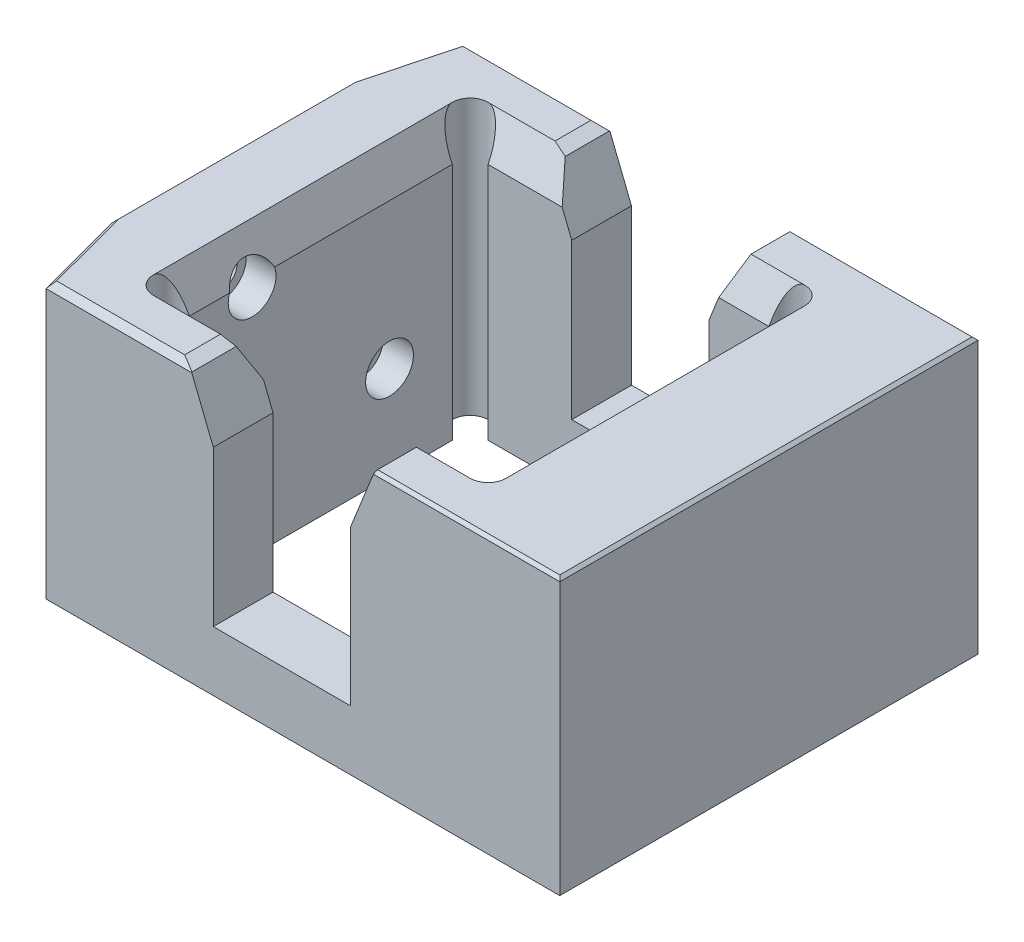
SolidWorks part; units mm, degrees
ref_plane "Front Plane" through (0, 0, 0) normal (0, 0, 1) x (1, 0, 0)
ref_plane "Top Plane" through (0, 0, 0) normal (0, 1, 0) x (1, 0, 0)
ref_plane "Right Plane" through (0, 0, 0) normal (1, 0, 0) x (0, 0, -1)
sketch "Sketch1" plane through (0, 0, 0) normal (0, 1, 0) x (1, 0, 0)
  line L1 (0, 0) -> (90, 0)
  line L2 (0, 0) -> (0, 70)
  line L3 (0, 70) -> (90, 70)
  line L4 (90, 0) -> (90, 70)
  dimension "D1" = 70
  dimension "D2" = 90
extrude "Boss-Extrude1" add sketch "Sketch1" along normal blind 46
sketch "Sketch2" plane through (0, 46, 0) normal (0, 1, 0) x (1, 0, 0)
  line L0 (90, 0) -> (90, 70) construction
  line L1 (15, 60) -> (68, 60)
  line L2 (15, 60) -> (15, 10)
  line L3 (15, 10) -> (68, 10)
  line L4 (68, 60) -> (68, 10)
  line L5 (90, 70) -> (0, 70) construction
  line L6 (0, 70) -> (0, 0) construction
  line L7 (0, 0) -> (90, 0) construction
  dimension "D1" = 22
  dimension "D2" = 10
  dimension "D3" = 15
  dimension "D4" = 10
extrude "Cut-Extrude1" cut sketch "Sketch2" against normal through all
sketch "Sketch3" plane through (0, 46, 0) normal (0, 1, 0) x (1, 0, 0)
  circle A0 centre (15, 60) radius 3
  circle A1 centre (68, 60) radius 3
  circle A2 centre (68, 10) radius 3
  circle A3 centre (15, 10) radius 3
  dimension "D1" = 6
extrude "Cut-Extrude2" cut sketch "Sketch3" against normal through all
sketch "Sketch4" plane through (0, 0, 0) normal (0, 0, 1) x (1, 0, 0)
  line L0 (0, 46) -> (90, 46) construction
  line L1 (32, 46) -> (55, 46)
  line L2 (32, 46) -> (32, 10)
  line L3 (32, 10) -> (55, 10)
  line L4 (55, 46) -> (55, 10)
  line L5 (90, 46) -> (90, 0) construction
  dimension "D1" = 23
  dimension "D2" = 36
  dimension "D3" = 35
extrude "Cut-Extrude3" cut sketch "Sketch4" against normal through all
chamfer "Chamfer1" distance 10 distance2 4 2 edges at (55, 46, -65) (55, 46, -5) first distance on face at (55, 28, -65) first distance on face at (55, 28, -5)
chamfer "Chamfer2" distance 4 distance2 10 2 edges at (32, 46, -65) (32, 46, -5) first distance on face at (18.6757, 46, -35)
chamfer "Chamfer3" distance 3 distance2 6 6 edges at (23, 46, -60) (15, 46, -35) (23, 46, -10) (62, 46, -10) (68, 46, -35) (62, 46, -60) first distance on face at (17.0757, 46, -35) first distance on face at (68.9243, 46, -35)
chamfer "Chamfer4" distance 4 distance2 15 1 edges at (0, 23, -70) first distance on face at (44.1, 27.6, -70)
chamfer "Chamfer5" distance 15 distance2 4 1 edges at (0, 23, 0) first distance on face at (0, 23, -27.5)
chamfer "Chamfer6" distance 1 angle 45 7 edges at (28, 46, -3.5) (28, 46, -66.5) (16, 46, -70) (2, 46, -62.5) (0, 46, -35) (2, 46, -7.5) (16, 46, 0) first distance on face at (30.08, 40.8, -5.4) first distance on face at (30.08, 40.8, -64.6) first distance on face at (44.9, 27.6, -70) first distance on face at (2, 23, -62.5) first distance on face at (0, 23, -35) first distance on face at (2, 23, -7.5) first distance on face at (44.9, 27.6, 0)
chamfer "Chamfer7" distance 0.5 angle 45 3 edges at (74.5, 46, -70) (90, 46, -35) (74.5, 46, 0)
sketch "Sketch5" plane through (0, 0, 0) normal (-1, 0, 0) x (0, 0, 1)
  line L0 (-15, 0) -> (-15, 45) construction
  line L1 (-15, 45) -> (-55, 45) construction
  line L2 (-55, 0) -> (-15, 0) construction
  line L3 (-55, 45) -> (-55, 0) construction
  circle A0 centre (-23.5, 38.65) radius 2.5
  circle A1 centre (-46.5, 15.65) radius 2.5
  point P4 (0, 0)
  point P6 (-23.4356, 38.5639)
  point P10 (-47.7854, 10.5737)
  dimension "D1" = 5
  dimension "D6" = 5
  dimension "D2" = 8.5
  dimension "D3" = 6.35
  dimension "D4" = 15.65
  dimension "D5" = 8.5
extrude "Cut-Extrude4" cut sketch "Sketch5" against normal blind 10
sketch "Sketch7" plane through (15, 0, 0) normal (1, 0, 0) x (0, 0, -1)
  circle A0 centre (23.5, 38.65) radius 4
  circle A1 centre (46.5, 15.65) radius 4
  dimension "D1" = 8
  dimension "D2" = 8
extrude "Cut-Extrude5" cut sketch "Sketch7" against normal blind 5
